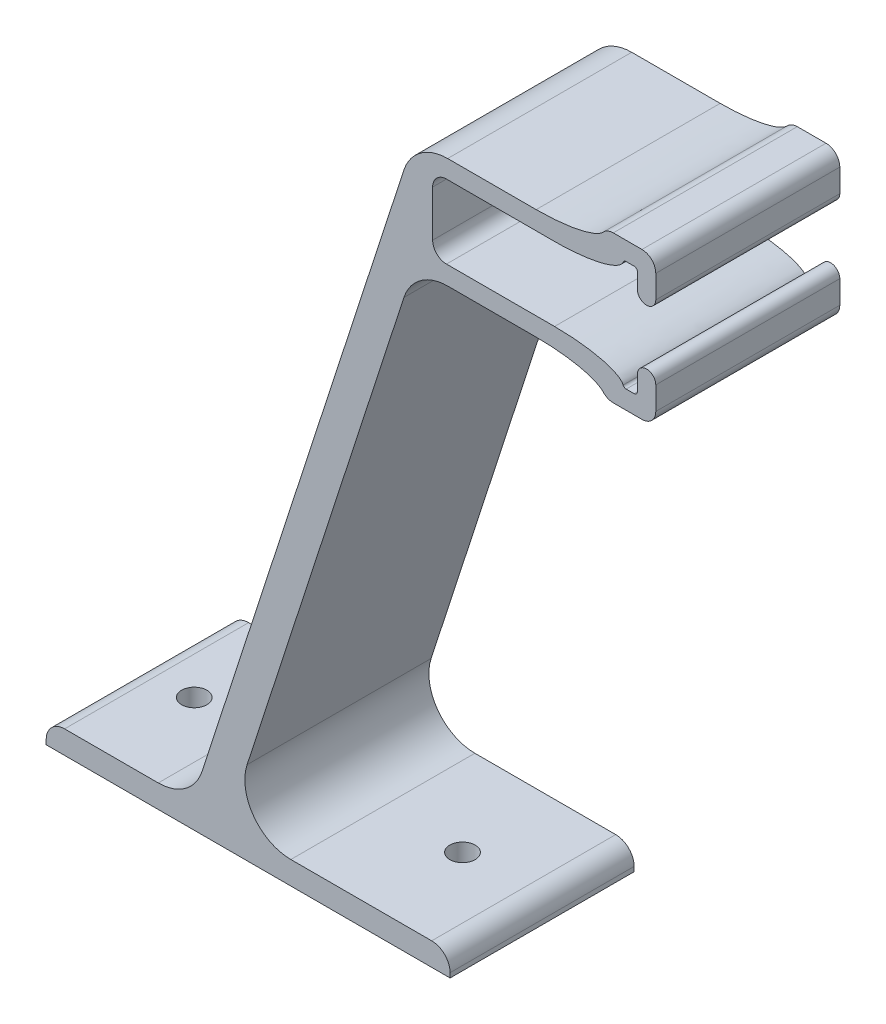
SolidWorks part; units mm, degrees
ref_plane "Front Plane" through (0, 0, 0) normal (0, 0, 1) x (1, 0, 0)
ref_plane "Top Plane" through (0, 0, 0) normal (0, 1, 0) x (1, 0, 0)
ref_plane "Right Plane" through (0, 0, 0) normal (1, 0, 0) x (0, 0, -1)
sketch "Sketch1" plane through (0, 0, 0) normal (0, 0, 1) x (1, 0, 0)
  line L0 (0, 0) -> (-42.2078, -130)
  line L1 (0, 0) -> (45.5, 0)
  line L2 (0, 0) -> (0, 24)
  line L3 (0, 24) -> (45.5, 24)
  line L12 (45.5, 0) -> (45.5, 24)
  line L13 (4, 4) -> (45.5, 4)
  line L14 (4, 4) -> (4, 20)
  line L15 (4, 20) -> (45.5, 20)
  line L16 (45.5, 4) -> (45.5, 20)
  line L17 (45.5, 20) -> (41.5, 20)
  line L18 (45.5, 20) -> (45.5, 28)
  line L19 (45.5, 28) -> (41.5, 28)
  line L20 (41.5, 20) -> (41.5, 28)
  line L21 (45.5, 4) -> (41.5, 4)
  line L22 (45.5, 4) -> (45.5, -4)
  line L23 (45.5, -4) -> (41.5, -4)
  line L24 (41.5, 4) -> (41.5, -4)
  line L25 (41.5, 28) -> (52.5, 28)
  line L26 (41.5, 28) -> (41.5, 24)
  line L27 (41.5, 24) -> (52.5, 24)
  line L28 (52.5, 28) -> (52.5, 24)
  line L29 (41.5, -4) -> (52.5, -4)
  line L30 (41.5, -4) -> (41.5, 0)
  line L31 (41.5, 0) -> (52.5, 0)
  line L32 (52.5, -4) -> (52.5, 0)
  line L33 (52.5, 24) -> (48.5, 24)
  line L34 (52.5, 24) -> (52.5, 20)
  line L35 (52.5, 20) -> (48.5, 20)
  line L36 (48.5, 24) -> (48.5, 20)
  line L37 (52.5, 0) -> (48.5, 0)
  line L38 (52.5, 0) -> (52.5, 4)
  line L39 (52.5, 4) -> (48.5, 4)
  line L40 (48.5, 0) -> (48.5, 4)
  line L41 (-42.2078, -130) -> (-50, -130)
  line L42 (-50, -130) -> (0, 24)
  line L44 (-80, -130) -> (7.7922, -130)
  line L45 (-80, -130) -> (-80, -125)
  line L46 (-80, -125) -> (7.7922, -125)
  line L47 (7.7922, -130) -> (7.7922, -125)
  arc A0 (48.5, 20) -> (52.5, 20) centre (50.5, 20) ccw
  arc A1 (48.5, 4) -> (52.5, 4) centre (50.5, 4) cw
  dimension "D6" = 4
  dimension "D10" = 4
  dimension "D11" = 4
  dimension "D1" = 4
  dimension "D2" = 4
  dimension "D3" = 4
  dimension "D4" = 16
  dimension "D5" = 41.5
  dimension "D7" = 4
  dimension "D8" = 4
  dimension "D9" = 4
  dimension "D12" = 11
  dimension "D13" = 11
  dimension "D14" = 4
  dimension "D15" = 4
  dimension "D16" = 130
  dimension "D17" = 50
  dimension "D18" = 5
  dimension "D19" = 30
  dimension "D20" = 50
extrude "Boss-Extrude1" add sketch "Sketch1" along normal blind 40
fillet "Fillet2" radius 15 1 edges at (45.5, 20, 20)
fillet "Fillet3" radius 4 1 edges at (45.5, 4, 20)
fillet "Fillet4" radius 4 1 edges at (41.5, 24, 20)
fillet "Fillet5" radius 15 1 edges at (41.5, 0, 20)
fillet "Fillet6" radius 3 2 edges at (4, 4, 20) (4, 20, 20)
fillet "Fillet7" radius 3 4 edges at (52.5, -4, 20) (52.5, 28, 20)
fillet "Fillet8" radius 0.7 4 edges at (48.5, 0, 20) (48.5, 24, 20)
fillet "Fillet9" radius 10 2 edges at (0, 0, 20) (0, 24, 20)
fillet "Fillet10" radius 10 2 edges at (-40.5844, -125, 20) (-48.3766, -125, 20)
sketch "Sketch2" plane through (0, -125, 0) normal (0, 1, 0) x (1, 0, 0)
  line L4 (-80, -20) -> (-55.6437, -20) construction
  line L5 (-80, -40) -> (-80, 0) construction
  line L6 (-55.6437, -40) -> (-55.6437, 0) construction
  line L7 (-26.8238, -20) -> (7.7922, -20) construction
  line L8 (-26.8238, 0) -> (-26.8238, -40) construction
  line L9 (7.7922, -40) -> (7.7922, 0) construction
  circle A0 centre (-67.8219, -20) radius 2.75
  circle A1 centre (-9.5158, -20) radius 2.75
  point P5 (-9.5158, -20)
  point P19 (-67.8219, -20)
  dimension "D1" = 5.5
  dimension "D2" = 5.5
extrude "Cut-Extrude1" cut sketch "Sketch2" against normal through all
fillet "Fillet11" radius 4 2 edges at (-80, -125, 20) (7.7922, -125, 20)
